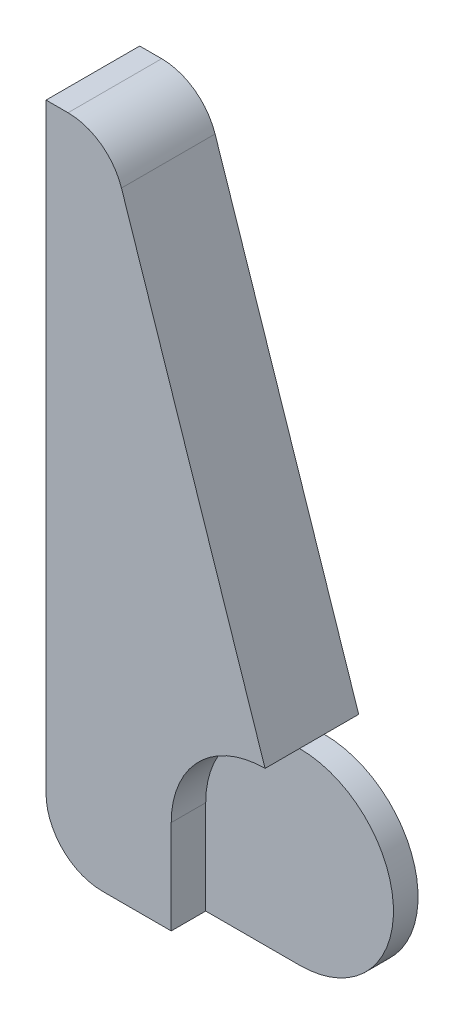
SolidWorks part; units mm, degrees
ref_plane "Front Plane" through (0, 0, 0) normal (0, 0, 1) x (1, 0, 0)
ref_plane "Top Plane" through (0, 0, 0) normal (0, 1, 0) x (1, 0, 0)
ref_plane "Right Plane" through (0, 0, 0) normal (1, 0, 0) x (0, 0, -1)
sketch "Sketch3" plane through (0, 0, 0) normal (0, 0, 1) x (1, 0, 0)
  line L0 (-1000, 0) -> (49000, 0) construction
  line L1 (0, -1000) -> (0, 49000) construction
  line L4 (0, -38.1) -> (-66.04, -38.1)
  line L5 (-88.9, -15.24) -> (-88.9, 228.6)
  line L6 (-88.9, 228.6) -> (-79.9766, 228.6)
  line L7 (-58.2897, 212.969) -> (0, 38.1)
  arc A0 (-79.9766, 228.6) -> (-58.2897, 212.969) centre (-79.9766, 205.74) cw
  arc A1 (0, -38.1) -> (0, 38.1) centre (0, 0) ccw
  arc A4 (-66.04, -38.1) -> (-88.9, -15.24) centre (-66.04, -15.24) cw
  point P21 (-63.5, 228.6)
  point P24 (-88.9, -38.1)
  dimension "D1" = 88.9
  dimension "D9" = 22.86
  dimension "D2" = 76.2
  dimension "D6" = 25.4
  dimension "D7" = 266.7
extrude "Boss-Extrude2" add sketch "Sketch3" along normal blind 19 and the other way blind 19
sketch "Sketch5" plane through (0, 0, 19) normal (0, 0, 1) x (1, 0, 0)
  line L0 (-38.1, 0) -> (-38.1, -38.1)
  line L2 (-38.1, -38.1) -> (0, -38.1)
  arc A0 (0, -38.1) -> (-38.1, 0) centre (0, 0) ccw
  arc A2 (0, -38.1) -> (0, 38.1) centre (0, 0) ccw construction
extrude "Cut-Extrude2" cut sketch "Sketch5" against normal offset from surface (14 mm away) 5 up to plane "Front Plane"
mirror "Mirror2" about plane through (0, 0, 0) normal (0, 0, 1) of "Cut-Extrude2"
sketch3d "3DSketch1"
  line L0 (0, 0, 190.5) -> (0, 0, -190.5)
  point P3 (0, 0, 0)
  dimension "D1" = 381
